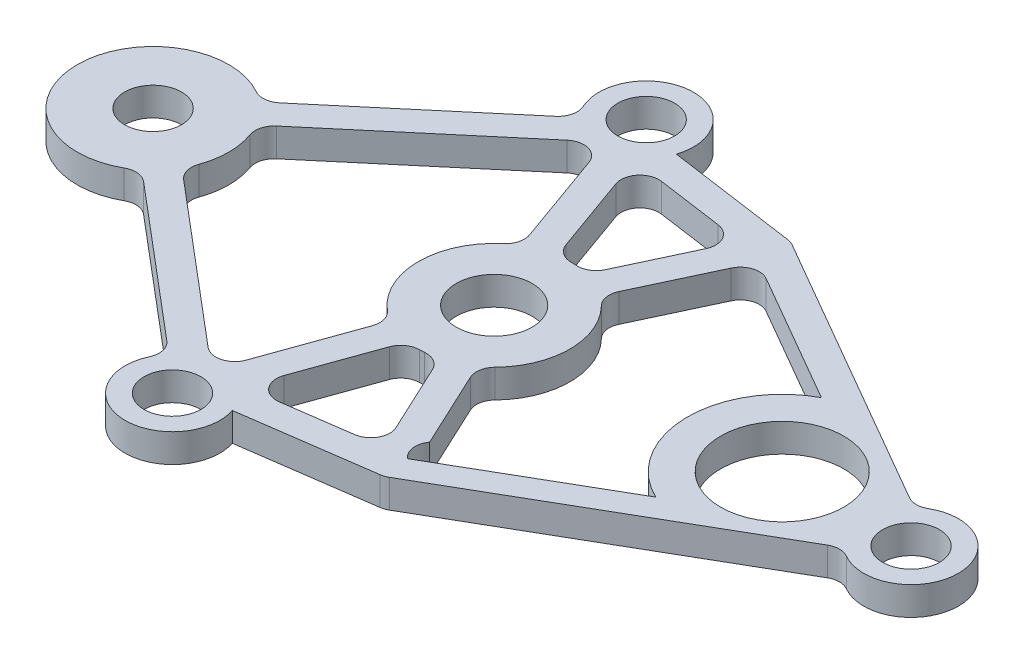
SolidWorks part; units mm, degrees
material "1060 Alloy"
ref_plane "Front" through (0, 0, 0) normal (0, 0, 1) x (1, 0, 0)
ref_plane "Top" through (0, 0, 0) normal (0, 1, 0) x (1, 0, 0)
ref_plane "Right" through (0, 0, 0) normal (1, 0, 0) x (0, 0, -1)
sketch "草图1" plane through (0, 0, 0) normal (0, 1, 0) x (1, 0, 0)
  line L0 (0, 0) -> (-18, 0) construction
  line L1 (0, 0) -> (22, 0) construction
  line L2 (22, 0) -> (4.6795, 10) construction
  line L4 (22, 0) -> (-4.4758, 12.5) construction
  line L5 (0, 0) -> (15.2, 0) construction
  line L6 (0.1065, -1.9972) -> (0.0924, -1.9669)
  line L7 (0.0811, -1.9984) -> (0.0924, -1.9669)
  line L8 (19.75, 2.1651) -> (5.0965, 10.6253)
  line L9 (4.7364, 10.7494) -> (-2.1019, 11.7159)
  line L10 (2.2314, 9.5886) -> (-1.2565, 10.0815)
  line L11 (4.9285, 10.7223) -> (-3.2584, 11.8794) construction
  line L12 (-7.0068, 10.2659) -> (-14.9056, 3.5951)
  line L13 (12.8531, 4.415) -> (5.9562, 8.3969)
  line L14 (4.5504, -7.9547) -> (2.6645, -3.9244)
  line L15 (-2.3379, -8.7543) -> (-0.8728, -4.6624)
  line L16 (2.9972, 8.1746) -> (1.3059, 4.5601)
  line L17 (-5.6221, 9.4721) -> (-13.9377, 2.4491)
  line L18 (-3.2584, 11.8794) -> (-4.5001, 14.0565) construction
  line L19 (-4.0354, -9.0452) -> (-2.285, -4.1568)
  line L20 (-4.5001, 14.0565) -> (-6.1038, 11.0285) construction
  line L21 (-4.9142, 10.0699) -> (-17.5161, -0.573) construction
  line L22 (-6.1038, 11.0285) -> (-18.4839, 0.573) construction
  line L23 (21.625, -0.6495) -> (4.4305, 9.2777) construction
  line L24 (22.375, 0.6495) -> (4.9285, 10.7223) construction
  line L25 (-5.6221, -9.4721) -> (-13.9377, -2.4491)
  line L27 (-4.4515, 10.9435) -> (-4.9142, 10.0699) construction
  line L28 (2.9972, -8.1746) -> (1.3059, -4.5601)
  line L29 (4.4305, 9.2777) -> (-4.1969, 10.4971) construction
  line L30 (13.0261, -4.5027) -> (4.7214, -9.2974)
  line L31 (-4.0354, 9.0452) -> (-2.285, 4.1568)
  line L32 (-7.0068, -10.2659) -> (-14.9056, -3.5951)
  line L33 (-2.3379, 8.7543) -> (-0.8728, 4.6624)
  line L34 (2.2314, -9.5886) -> (-1.2565, -10.0815)
  line L35 (4.5504, 7.9547) -> (2.6645, 3.9244)
  line L38 (4.7364, -10.7494) -> (-2.1019, -11.7159)
  line L39 (19.75, -2.1651) -> (5.0965, -10.6253)
  line L41 (-4.1969, 10.4971) -> (-4.4515, 10.9435) construction
  line L42 (-3.7277, 11.1883) -> (-4.4758, 12.5) construction
  line L43 (-4.4758, 12.5) -> (-5.509, 10.5492) construction
  line L44 (4.6795, 10) -> (-3.7277, 11.1883) construction
  line L45 (-5.509, 10.5492) -> (-18, 0) construction
  circle A0 centre (0, 0) radius 2
  arc A1 (0.3201, 3.9872) -> (0.0549, 3.9996) centre (0, 0) ccw
  circle A2 centre (-18, 0) radius 1.5
  arc A3 (-16.0406, 3.4872) -> (-16.0406, -3.4872) centre (-18, 0) ccw
  circle A4 centre (22, 0) radius 1.5
  arc A5 (20.75, -2.1651) -> (20.75, 2.1651) centre (22, 0) ccw
  arc A7 (-2.5812, 3.0557) -> (-2.5812, -3.0557) centre (0, 0) ccw
  arc A8 (-2.1019, 11.7159) -> (-6.7446, 11.4499) centre (-4.4758, 12.5) ccw
  circle A9 centre (-4.4758, 12.5) radius 1.5
  arc A10 (19.75, 2.1651) -> (20.75, 2.1651) centre (20.25, 3.0311) ccw
  arc A12 (-13.9377, 2.4491) -> (-14.234, 1.3481) centre (-13.2925, 1.6851) ccw
  arc A13 (-14.9056, 3.5951) -> (-16.0406, 3.4872) centre (-15.5508, 4.3591) cw
  arc A14 (-7.0068, 10.2659) -> (-6.7446, 11.4499) centre (-7.6521, 11.0299) ccw
  arc A15 (-2.285, 4.1568) -> (-2.5812, 3.0557) centre (-3.2265, 3.8197) cw
  arc A16 (2.8562, 2.8004) -> (2.6645, 3.9244) centre (3.5702, 3.5005) cw
  arc A17 (0.3201, 3.9872) -> (1.3059, 4.5601) centre (0.4001, 4.984) ccw
  arc A18 (-0.8728, 4.6624) -> (0.0549, 3.9996) centre (0.0687, 4.9995) ccw
  arc A19 (4.5504, 7.9547) -> (5.9562, 8.3969) centre (5.4562, 7.5309) cw
  arc A20 (5.0965, 10.6253) -> (4.7364, 10.7494) centre (4.5965, 9.7592) ccw
  arc A21 (2.2314, 9.5886) -> (2.9972, 8.1746) centre (2.0915, 8.5984) cw
  arc A22 (-1.2565, 10.0815) -> (-2.3379, 8.7543) centre (-1.3965, 9.0914) ccw
  arc A23 (-4.0354, 9.0452) -> (-5.6221, 9.4721) centre (-4.9768, 8.7081) ccw
  arc A24 (2.8562, -2.8004) -> (2.8562, 2.8004) centre (0, 0) ccw
  arc A25 (-14.234, -1.3481) -> (-14.234, 1.3481) centre (-18, 0) ccw
  arc A26 (-4.0354, -9.0452) -> (-5.6221, -9.4721) centre (-4.9768, -8.7081) cw
  arc A27 (-1.2565, -10.0815) -> (-2.3379, -8.7543) centre (-1.3965, -9.0914) cw
  arc A28 (2.2314, -9.5886) -> (2.9972, -8.1746) centre (2.0915, -8.5984) ccw
  arc A29 (5.0965, -10.6253) -> (4.7364, -10.7494) centre (4.5965, -9.7592) cw
  arc A30 (4.5504, -7.9547) -> (4.7214, -9.2974) centre (5.3662, -8.5331) ccw
  arc A31 (-0.8728, -4.6624) -> (0.0549, -3.9996) centre (0.0687, -4.9995) cw
  arc A32 (0.3201, -3.9872) -> (1.3059, -4.5601) centre (0.4001, -4.984) cw
  arc A33 (2.8562, -2.8004) -> (2.6645, -3.9244) centre (3.5702, -3.5005) ccw
  arc A34 (-2.285, -4.1568) -> (-2.5812, -3.0557) centre (-3.2265, -3.8197) ccw
  arc A35 (-7.0068, -10.2659) -> (-6.7446, -11.4499) centre (-7.6521, -11.0299) cw
  arc A36 (-14.9056, -3.5951) -> (-16.0406, -3.4872) centre (-15.5508, -4.3591) ccw
  arc A37 (-13.9377, -2.4491) -> (-14.234, -1.3481) centre (-13.2925, -1.6851) cw
  arc A38 (19.75, -2.1651) -> (20.75, -2.1651) centre (20.25, -3.0311) cw
  circle A39 centre (-4.4758, -12.5) radius 1.5
  arc A40 (-2.1019, -11.7159) -> (-6.7446, -11.4499) centre (-4.4758, -12.5) cw
  arc A41 (0.3201, -3.9872) -> (0.0549, -3.9996) centre (0, 0) cw
  circle A42 centre (15.2, 0) radius 3.25
  arc A45 (12.8531, 4.415) -> (13.0261, -4.5027) centre (15.2, 0) ccw
  point P53 (-2.0306, 3.4463)
  point P79 (-2.0306, -3.4463)
  dimension "D1" = 30
  dimension "D2" = 0.75
  dimension "D4" = 1
  dimension "D6" = 15.2
  dimension "D7" = 3
  dimension "D8" = 5
  dimension "D9" = 6.5
  dimension "D5" = 25.273
  dimension "D3" = 0.75
extrude "凸台-拉伸1" add sketch "草图1" along normal blind 1.5 contours A40 L38 A29 L39 A38 A5 A10 L8 A20 L9 A8 A14 L12 A13 A3 A36 L32 A35 A41 A32 L28 A28 L34 A27 L15 A31 L25 A37 A25 A12 L17 A23 L31 A15 A7 A34 L19 A26 A0 A2 A4 A9 A22 region at (20.25, 0, -1.4777)
